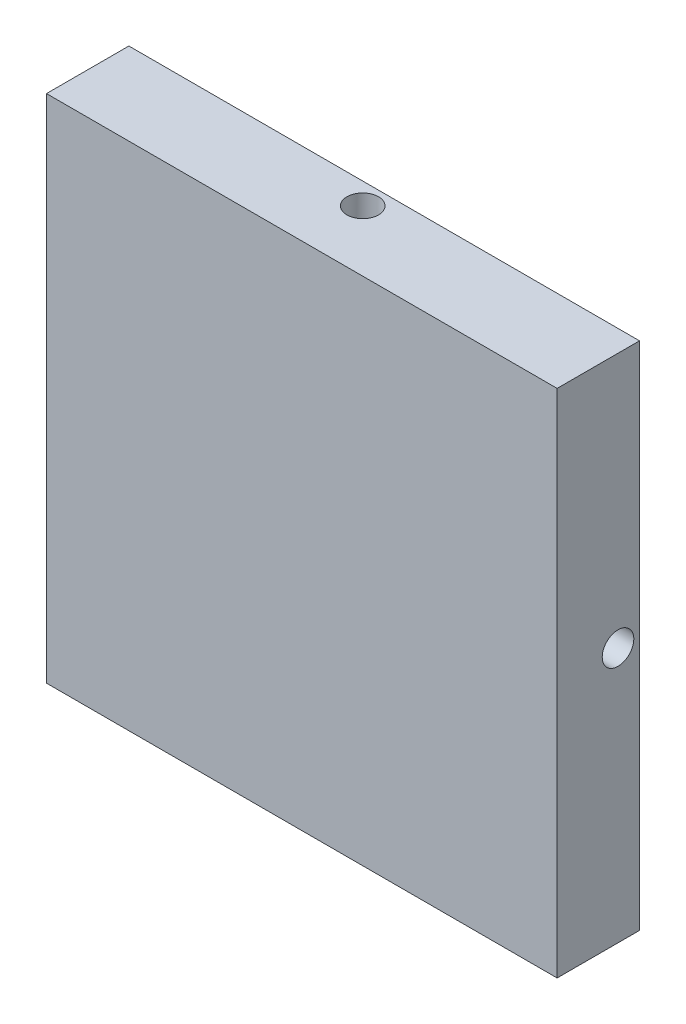
SolidWorks part; units mm, degrees
note: The reader was unsure of these and kept them because the rebuilt part matched: shared geometry of "Sketch1<3>", "Sketch1<4>".
ref_plane "Front Plane" through (0, 0, 0) normal (0, 0, 1) x (1, 0, 0)
ref_plane "Top Plane" through (0, 0, 0) normal (0, 1, 0) x (1, 0, 0)
ref_plane "Right Plane" through (0, 0, 0) normal (1, 0, 0) x (0, 0, -1)
sketch "Sketch1" plane through (0, 0, 0) normal (0, 0, 1) x (1, 0, 0)
  line L0 (0, 0) -> (13.031, -35.8023) construction
  line L1 (-56.5785, 56.5785) -> (56.5785, 56.5785)
  line L2 (-56.5785, 56.5785) -> (-56.5785, -56.5785)
  line L3 (-56.5785, -56.5785) -> (56.5785, -56.5785)
  line L4 (56.5785, 56.5785) -> (56.5785, -56.5785)
  line L5 (0, 0) -> (0, -50.8) construction
  line L6 (-27.4443, 50.8) -> (31.5245, 50.8) construction
  line L7 (0, 0) -> (-14.2043, -16.9281) construction
  circle A0 centre (0, 0) radius 50.8
  circle A1 centre (13.031, -35.8023) radius 3.0163
  circle A2 centre (0, 0) radius 3.0162
  circle A3 centre (-37.5212, 6.616) radius 3.0163
  circle A4 centre (24.4902, 29.1863) radius 3.0163
  circle A5 centre (-43.8785, 43.8785) radius 3.3337
  circle A6 centre (43.8785, 43.8785) radius 3.3337
  circle A7 centre (43.8785, -43.8785) radius 3.3337
  circle A8 centre (-43.8785, -43.8785) radius 3.3337
  circle A9 centre (-14.2043, -16.9281) radius 3.048
  point P12 (0, 56.5785)
  point P18 (0, 0)
  point P23 (-56.5785, 0)
  point P29 (0, 0)
  dimension "D1" = 101.6
  dimension "D4" = 6.0325
  dimension "D5" = 6.0325
  dimension "D7" = 6.6675
  dimension "D14" = 6.096
  dimension "D2" = 38.1
  dimension "D3" = 20
  dimension "D8" = 12.7
  dimension "D9" = 90
  dimension "D10" = 12.7
  dimension "D11" = 4
  dimension "D12" = 56.5785
  dimension "D13" = 5.7785
  dimension "D15" = 22.098
  dimension "D16" = 60
  dimension "D6" = 3
extrude "Boss-Extrude1" add sketch "Sketch1" along normal blind 8.7312 contours L4 L1 L2 L3 A8 A7 A6 A5 A0 | A6 | A5 | A8 | A7 | A1 | A3 | A4 | A0 A4 A3 A2 A1 | A2
extrude "Boss-Extrude2" add sketch "Sketch1<3>" against normal blind 9.525 contours L4 L1 L2 L3 A8 A7 A6 A5 A0 | A4 | A1 | A2 | A3 | A9
sketch "Sketch1<3>" plane through (0, 0, 0) normal (0, 0, 1) x (1, 0, 0) same geometry as "Sketch1"
extrude "Boss-Extrude3" add sketch "Sketch1<4>" against normal blind 18.3515 contours A2
sketch "Sketch1<4>" plane through (0, 0, 0) normal (0, 0, 1) x (1, 0, 0) same geometry as "Sketch1"
sketch "Sketch2" plane through (0, 56.5785, 0) normal (0, 1, 0) x (1, 0, 0)
  line L0 (-56.5785, 9.525) -> (56.5785, 9.525) construction
  circle A0 centre (0, 4.7625) radius 3.5
  dimension "D1" = 7
  dimension "D2" = 4.7625
extrude "Cut-Extrude1" cut sketch "Sketch2" against normal up to next
pattern_circular "CirPattern1" count 4 over 360 about axis through (0, 0, -9.525) along (0, 0, 1) of "Cut-Extrude1"
sketch "Sketch4" plane through (0, 0, 0) normal (0, 0, -1) x (-1, 0, 0)
  line L0 (-46.8941, 0) -> (-25.0102, 0) construction
  line L1 (-46.8941, 1.27) -> (-25.0102, 1.27)
  line L2 (-46.8941, -1.27) -> (-25.0102, -1.27)
  arc A0 (-46.8941, 1.27) -> (-46.8941, -1.27) centre (-46.8941, 0) ccw
  arc A1 (-25.0102, -1.27) -> (-25.0102, 1.27) centre (-25.0102, 0) ccw
  point P2 (-35.9522, 0)
  dimension "D1" = 2.54
extrude "Cut-Extrude2" [suppressed] cut sketch "Sketch4" against normal blind 5.08
fillet "Fillet3" [suppressed] radius 1.905
sketch "Sketch5" plane through (0, 0, 8.7312) normal (0, 0, 1) x (1, 0, 0)
  circle A0 centre (-14.2043, -16.9281) radius 3.048
  point P0 (-14.2043, -16.9281)
extrude "Boss-Extrude4" add sketch "Sketch5" against normal blind 9.525
